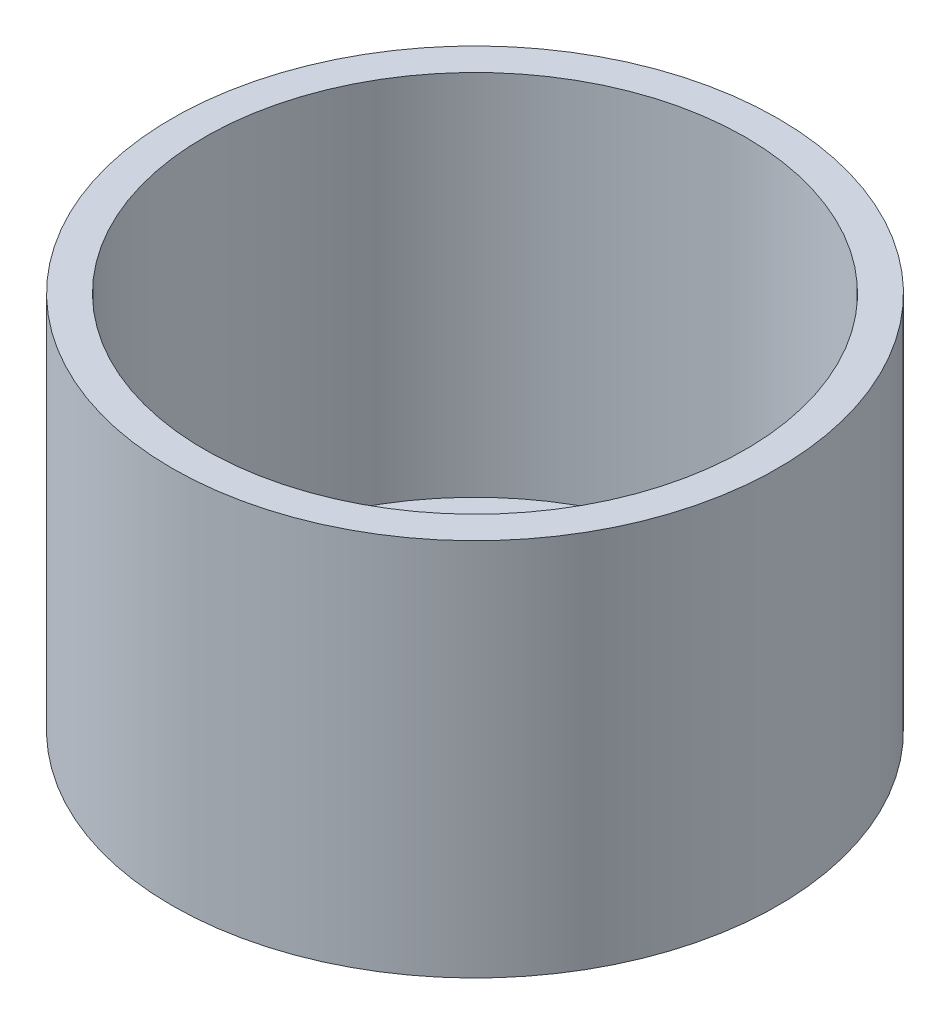
SolidWorks part; units mm, degrees
material "Alumina"
ref_plane "Front Plane" through (0, 0, 0) normal (0, 0, 1) x (1, 0, 0)
ref_plane "Top Plane" through (0, 0, 0) normal (0, 1, 0) x (1, 0, 0)
ref_plane "Right Plane" through (0, 0, 0) normal (1, 0, 0) x (0, 0, -1)
sketch "Sketch1" plane through (0, 0, 0) normal (0, 1, 0) x (1, 0, 0)
  line L1 (-125, -125) -> (125, -125)
  line L2 (-125, -125) -> (-125, 125)
  line L3 (-125, 125) -> (125, 125)
  line L4 (125, -125) -> (125, 125)
  line L5 (-125, -125) -> (125, 125) construction
  line L6 (-125, 125) -> (125, -125) construction
  point P0 (0, 0)
  dimension "D1" = 250
  dimension "D2" = 250
extrude "Boss-Extrude1" add sketch "Sketch1" along normal blind 5
sketch "Sketch8" plane through (0, 5, 0) normal (0, 1, 0) x (1, 0, 0)
  circle A1 centre (0, -95) radius 10 construction
  circle A2 centre (99.779, -1.1471) radius 7.5
  circle A3 centre (0, -95) radius 7.5
  ellipse E1 centre (99.779, -1.1471) end of major axis (89.9596, 0.745) minor radius 9.9963 construction
  dimension "D1" = 15
  dimension "D2" = 15
extrude "Boss-Extrude3" add sketch "Sketch8" along normal blind 5
sketch "Sketch9" plane through (0, 0, 0) normal (1, 0, 0) x (0, 0, -1)
  line L0 (-95, 10) -> (-95, -6.6364) construction
  line L1 (-87.5, 10) -> (-102.5, 10) construction
  line L2 (-95, 15) -> (-95, 5)
  arc A0 (-95, 15) -> (-95, 5) centre (-95, 10) ccw
  dimension "D1" = 10
revolve "Cut-Revolve3" cut sketch "Sketch9" angle 360 about L0
ref_plane "Plane1" through (0, 0, 1.05) normal (0, 0, 1) x (1, 0, 0)
sketch "Sketch10" plane through (0, 0, 1.05) normal (0, 0, 1) x (1, 0, 0)
  line L0 (99.779, 15) -> (99.779, 5)
  line L1 (107.279, 10) -> (92.279, 10) construction
  arc A0 (99.779, 15) -> (99.779, 5) centre (99.779, 10) ccw
  dimension "D1" = 10
revolve "Cut-Revolve4" cut sketch "Sketch10" angle 360 about L0
fillet "Fillet6" radius 2 2 edges at (99.779, 5, -6.3529) (0, 5, 87.5)
fillet "Fillet7" radius 0.5 2 edges at (99.779, 10, 8.6471) (0, 10, 102.5)
sketch "Sketch11" plane through (0, 5, 0) normal (0, 1, 0) x (1, 0, 0)
  line L4 (125, -125) -> (125, 125)
  line L5 (125, 125) -> (-125, 125)
  line L6 (-125, 125) -> (-125, -125)
  line L7 (-125, -125) -> (125, -125)
  line L8 (125, -125) -> (125, 125)
  line L9 (125, 125) -> (-125, 125)
  line L10 (-125, 125) -> (-125, -125)
  line L11 (-125, -125) -> (125, -125)
  circle A0 centre (-47.523, 40.2081) radius 2.5 construction
  circle A1 centre (-19.2407, 30.2025) radius 2.5 construction
  circle A2 centre (-9.2351, 58.4849) radius 2.5 construction
  circle A3 centre (-37.5174, 68.4904) radius 2.5 construction
  circle A4 centre (-47.523, 40.2081) radius 2.5
  circle A5 centre (-19.2407, 30.2025) radius 2.5
  circle A6 centre (-9.2351, 58.4849) radius 2.5
  circle A7 centre (-37.5174, 68.4904) radius 2.5
  dimension "D1" = 0
extrude "Cut-Extrude4" cut sketch "Sketch11" against normal blind 10 contours A5 | A7 | A4 | A6 region at (-19.2407, 5, -30.2025) region at (-37.5174, 5, -68.4904)
sketch "Sketch12" plane through (0, 0, 0) normal (0, -1, 0) x (-1, 0, 0)
  circle A0 centre (0, 0) radius 125
extrude "Cut-Extrude5" cut sketch "Sketch12" against normal blind 10 flip side to cut
sketch "Sketch13" plane through (0, 0, 0) normal (0, -1, 0) x (1, 0, 0)
  circle A0 centre (0, 0) radius 125
  circle A1 centre (0, 0) radius 140
extrude "Boss-Extrude4" add sketch "Sketch13" against normal blind 175
sketch "Sketch15" plane through (0, 175, 0) normal (0, 1, 0) x (1, 0, 0)
  circle A0 centre (0, 0) radius 140
  circle A1 centre (0, 0) radius 100
  dimension "D1" = 280
